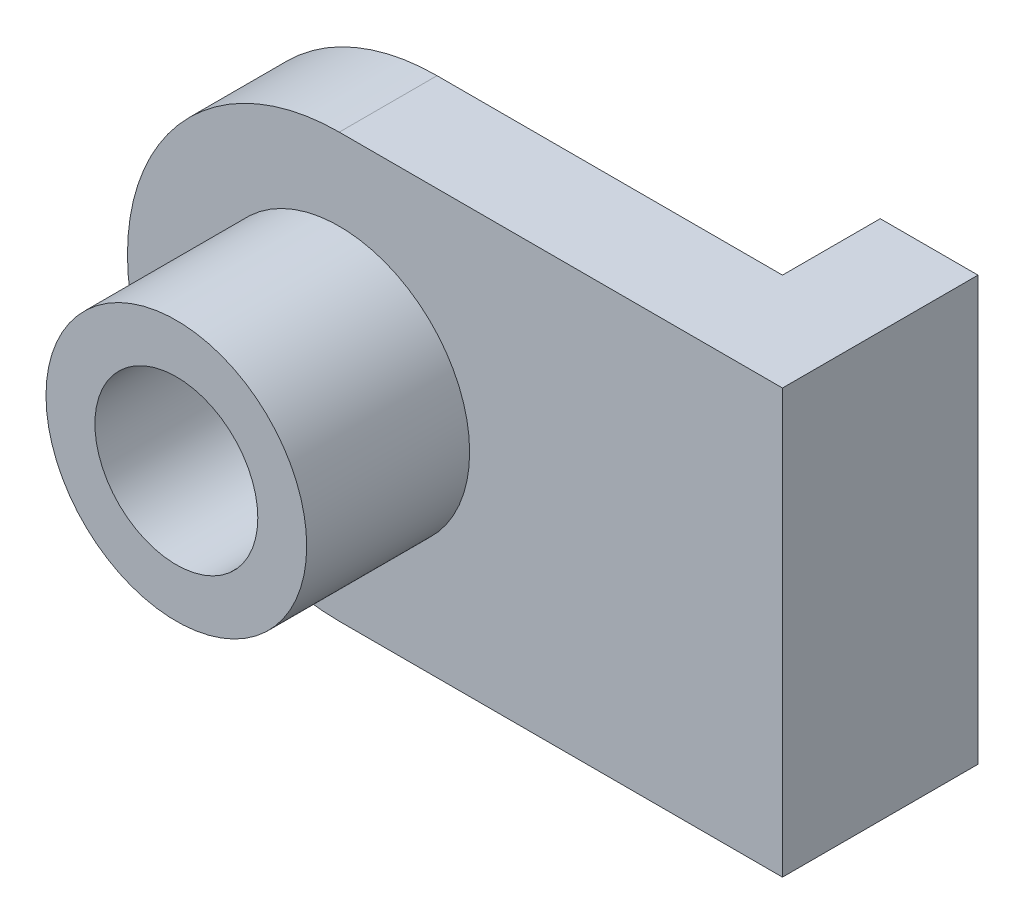
SolidWorks part; units mm, degrees
ref_plane "Front Plane" through (0, 0, 0) normal (0, 0, 1) x (1, 0, 0)
ref_plane "Top Plane" through (0, 0, 0) normal (0, 1, 0) x (1, 0, 0)
ref_plane "Right Plane" through (0, 0, 0) normal (1, 0, 0) x (0, 0, -1)
sketch "Sketch1" plane through (0, 0, 0) normal (0, 0, 1) x (1, 0, 0)
  line L0 (0, 0) -> (1727.2, 0)
  line L1 (1727.2, 0) -> (1727.2, 1651)
  line L2 (1727.2, 1651) -> (0, 1651)
  arc A0 (0, 1651) -> (0, 0) centre (0, 825.5) ccw
  dimension "D1" = 1651
  dimension "D2" = 1727.2
extrude "Boss-Extrude1" add sketch "Sketch1" along normal blind 381
sketch "Sketch2" plane through (0, 0, 381) normal (0, 0, 1) x (1, 0, 0)
  circle A0 centre (0, 825.5) radius 508
  dimension "D1" = 1016
extrude "Boss-Extrude2" add sketch "Sketch2" along normal blind 635
sketch "Sketch3" plane through (0, 0, 1016) normal (0, 0, 1) x (1, 0, 0)
  circle A0 centre (0, 825.5) radius 317.5
  dimension "D1" = 635
extrude "Cut-Extrude1" cut sketch "Sketch3" against normal through all
sketch "Sketch4" plane through (0, 0, 0) normal (0, 0, -1) x (-1, 0, 0)
  line L0 (-1727.2, 1651) -> (-1346.2, 1651)
  line L1 (-1727.2, 1651) -> (0, 1651) construction
  line L2 (-1346.2, 1651) -> (-1346.2, 0)
  line L3 (0, 0) -> (-1727.2, 0) construction
  line L4 (-1346.2, 0) -> (-1727.2, 0)
  line L5 (-1727.2, 0) -> (-1727.2, 1651)
  dimension "D1" = 381
extrude "Boss-Extrude3" add sketch "Sketch4" along normal blind 381 contours L2 L4 L5 L0
